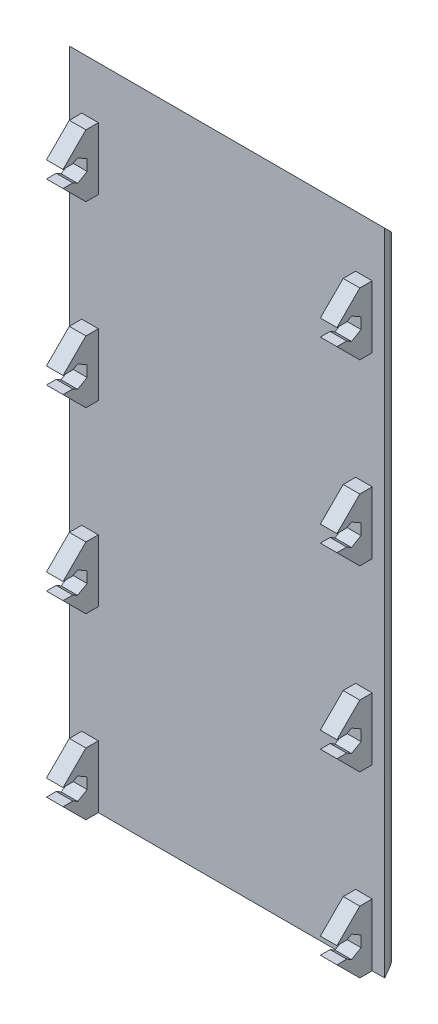
SolidWorks part; units mm, degrees
ref_plane "Front Plane" through (0, 0, 0) normal (0, 0, 1) x (1, 0, 0)
ref_plane "Top Plane" through (0, 0, 0) normal (0, 1, 0) x (1, 0, 0)
ref_plane "Right Plane" through (0, 0, 0) normal (1, 0, 0) x (0, 0, -1)
sketch "Sketch1" plane through (0, 0, 0) normal (0, 1, 0) x (1, 0, 0)
  line L0 (-9.2151, 0) -> (-9.2151, -10)
  line L1 (-9.2151, -10) -> (-5.2151, -10)
  line L2 (-5.2151, -10) -> (-5.2151, 0)
  line L3 (-5.2151, 0) -> (56.7849, 0)
  line L4 (56.7849, 0) -> (56.7849, -10)
  line L5 (56.7849, -10) -> (60.7849, -10)
  line L6 (60.7849, -10) -> (60.7849, 0)
  line L7 (60.7849, 0) -> (63.7849, 0)
  line L8 (-9.2151, 0) -> (-12.2151, 0)
  line L9 (-12.2151, 0) -> (-8.1737, 7)
  line L10 (-8.1737, 7) -> (59.7434, 7)
  line L11 (59.7434, 7) -> (63.7849, 0)
  line L12 (25.7849, 7) -> (25.7849, 0) construction
  dimension "D1" = 3
  dimension "D2" = 10
  dimension "D3" = 70
  dimension "D4" = 7
  dimension "D5" = 4
  dimension "D6" = 60
extrude "Boss-Extrude1" add sketch "Sketch1" along normal blind 156.5
sketch "Sketch4" plane through (60.7849, 0, 0) normal (1, 0, 0) x (0, 0, -1)
  line L0 (0, 156.5) -> (0, 0) construction
  line L1 (-37.5185, 156.5) -> (0, 156.5)
  line L2 (-37.5185, 156.5) -> (-37.5185, 144)
  line L3 (-37.5185, 144) -> (0, 144)
  line L4 (0, 156.5) -> (0, 144)
  line L5 (-37.5185, 156.5) -> (0, 144) construction
  line L6 (-37.5185, 144) -> (0, 156.5) construction
  line L7 (-10, 156.5) -> (0, 156.5) construction
  point P0 (-18.7592, 150.25)
  dimension "D1" = 12.5
extrude "Cut-Extrude1" cut sketch "Sketch4" against normal through all
sketch "Sketch5" plane through (60.7849, 0, 0) normal (1, 0, 0) x (0, 0, -1)
  line L0 (0, 156.5) -> (0, 0) construction
  line L1 (-33.3149, 129) -> (0, 129)
  line L2 (-33.3149, 129) -> (-33.3149, 101)
  line L3 (-33.3149, 101) -> (0, 101)
  line L4 (0, 129) -> (0, 101)
  line L5 (-33.3149, 129) -> (0, 101) construction
  line L6 (-33.3149, 101) -> (0, 129) construction
  line L7 (-10, 144) -> (0, 144) construction
  point P0 (-16.6574, 115)
  dimension "D1" = 28
  dimension "D2" = 15
extrude "Cut-Extrude2" cut sketch "Sketch5" against normal through all
sketch "Sketch6" plane through (0, 0, 0) normal (1, 0, 0) x (0, 0, -1)
  line L0 (-10, 144) -> (-10, 129) construction
  line L1 (-2.7, 137.8279) -> (-5, 139.1558)
  line L2 (-5, 139.1558) -> (-7.3, 137.8279)
  line L3 (-7.3, 137.8279) -> (-7.3, 135.1721)
  line L4 (-7.3, 135.1721) -> (-5, 133.8442)
  line L5 (-5, 133.8442) -> (-2.7, 135.1721)
  line L6 (-2.7, 135.1721) -> (-2.7, 137.8279)
  line L7 (-10, 144) -> (0, 144) construction
  line L8 (-6.15, 138.4919) -> (-10, 138.4919)
  line L9 (-6.15, 134.5081) -> (-10, 134.5081)
  line L10 (-10, 134.5081) -> (-10, 138.4919)
  circle A1 centre (-5, 136.5) radius 2.3 construction
  dimension "D1" = 4.6
  dimension "D2" = 7.5
  dimension "D3" = 5
extrude "Cut-Extrude3" cut sketch "Sketch6" against normal through all and the other way through all contours L10 L9 L4 L3 L2 L8 | L5 L6 L1 L2 L3 L4 region at (0, 136.5, 5) region at (0, 136.5, 8.5351)
pattern_linear "LPattern1" count 4 spacing 43 along (0, -1, 0) of "Cut-Extrude2", "Cut-Extrude3"
chamfer "Chamfer3" distance 7 angle 45 1 edges at (25.7849, 156.5, -7)
fillet "Fillet1" radius 8 2 edges at (-8.1737, 74.75, -7) (59.7434, 74.75, -7)
chamfer "Chamfer5" distance 7 angle 45 16 edges at (58.7849, 43, 10) (58.7849, 144, 10) (58.7849, 129, 10) (-7.2151, 144, 10) (-7.2151, 129, 10) (-7.2151, 101, 10) (-7.2151, 86, 10) (58.7849, 101, 10) (58.7849, 86, 10) (58.7849, 58, 10) (58.7849, 0, 10) (58.7849, 15, 10) (-7.2151, 0, 10) (-7.2151, 15, 10) (-7.2151, 58, 10) (-7.2151, 43, 10)
sketch "Sketch7" plane through (0, 0, -7) normal (0, 0, -1) x (-1, 0, 0)
  line L8 (3.5549, 82.737) -> (-11.316, 82.737) construction
  line L14 (-11.316, 128.6101) -> (-40.2538, 128.6101) construction
  line L20 (-11.316, 128.6101) -> (-11.316, 82.737) construction
  line L22 (-40.2538, 128.6101) -> (-40.2538, 82.737) construction
  line L23 (-11.316, 82.737) -> (-40.2538, 82.737) construction
  line L24 (3.5549, 0) -> (3.5549, 149.5) construction
  line L25 (-11.316, 127.6101) -> (-11.316, 116.1874)
  line L26 (-12.316, 128.6101) -> (-39.2538, 128.6101)
  line L27 (-11.316, 115.6101) -> (-40.2538, 115.6101) construction
  line L28 (-40.2538, 127.6101) -> (-40.2538, 115.6101)
  line L29 (-40.2538, 82.737) -> (-55.1246, 82.737) construction
  line L30 (-55.1246, 149.5) -> (-55.1246, 0) construction
  line L31 (-11.316, 149.5) -> (-11.316, 128.6101) construction
  line L32 (3.5549, 149.5) -> (-55.1246, 149.5) construction
  line L35 (-11.316, 107.5272) -> (-17.816, 103.7744)
  line L38 (-25.316, 99.4443) -> (-39.7538, 91.1086)
  line L39 (-11.316, 107.5272) -> (-11.316, 93.237)
  line L40 (-40.2538, 90.2426) -> (-40.2538, 82.737)
  line L41 (-40.2538, 82.737) -> (-32.316, 87.3199)
  line L42 (-32.316, 87.3199) -> (-32.316, 93.237) construction
  line L43 (-18.316, 102.9084) -> (-18.316, 93.237)
  line L44 (-11.316, 93.237) -> (-32.316, 93.237) construction
  line L45 (-25.316, 99.4443) -> (-25.316, 93.237)
  line L46 (-18.316, 93.237) -> (-25.316, 93.237) construction
  line L47 (-39.7538, 107.2744) -> (-18.566, 119.5072)
  line L48 (-40.2538, 115.6101) -> (-40.2538, 106.9857) construction
  line L49 (-11.316, 82.737) -> (-40.2538, 82.737) construction
  line L50 (-40.2538, 106.4084) -> (-40.2538, 100.5631)
  line L51 (-32.316, 87.3199) -> (-30.9714, 88.0962)
  line L52 (-11.816, 115.3214) -> (-31.566, 103.9187)
  line L53 (-33.2538, 121.1101) -> (-33.2538, 119.3988)
  line L54 (-31.566, 103.0527) -> (-25.316, 99.4443)
  line L55 (-32.316, 95.4028) -> (-39.7538, 99.6971)
  line L56 (-33.5038, 118.9657) -> (-40.2538, 115.0686)
  line L57 (-40.2538, 115.0686) -> (-40.2538, 115.6101)
  line L58 (-32.7538, 121.6101) -> (-18.816, 121.6101)
  line L59 (-18.316, 121.1101) -> (-18.316, 119.9402)
  line L60 (-11.316, 121.6101) -> (-18.316, 121.6101) construction
  line L61 (-33.2538, 121.6101) -> (-40.2538, 121.6101) construction
  line L62 (-40.2538, 128.6101) -> (-11.316, 128.6101) construction
  line L63 (-11.316, 128.6101) -> (-11.316, 82.737) construction
  arc A7 (-11.316, 93.237) -> (-32.316, 93.237) centre (-21.816, 93.237) cw
  arc A8 (-18.316, 93.237) -> (-25.316, 93.237) centre (-21.816, 93.237) cw
  arc A9 (-17.816, 103.7744) -> (-18.316, 102.9084) centre (-17.316, 102.9084) ccw
  arc A10 (-11.816, 115.3214) -> (-11.316, 116.1874) centre (-12.316, 116.1874) ccw
  arc A11 (-11.316, 127.6101) -> (-12.316, 128.6101) centre (-12.316, 127.6101) ccw
  arc A12 (-39.7538, 91.1086) -> (-40.2538, 90.2426) centre (-39.2538, 90.2426) ccw
  arc A13 (-39.2538, 128.6101) -> (-40.2538, 127.6101) centre (-39.2538, 127.6101) ccw
  arc A14 (-40.2538, 106.4084) -> (-39.7538, 107.2744) centre (-39.2538, 106.4084) cw
  arc A15 (-39.7538, 99.6971) -> (-40.2538, 100.5631) centre (-39.2538, 100.5631) cw
  arc A16 (-32.7538, 121.6101) -> (-33.2538, 121.1101) centre (-32.7538, 121.1101) ccw
  arc A17 (-33.5038, 118.9657) -> (-33.2538, 119.3988) centre (-33.7538, 119.3988) ccw
  arc A18 (-18.316, 121.1101) -> (-18.816, 121.6101) centre (-18.816, 121.1101) ccw
  arc A19 (-18.566, 119.5072) -> (-18.316, 119.9402) centre (-18.816, 119.9402) ccw
  arc A20 (-31.566, 103.0527) -> (-31.566, 103.9187) centre (-31.316, 103.4857) cw
  point P59 (-40.2538, 106.9857)
  point P63 (-40.2538, 99.9857)
  dimension "D11" = 7
  dimension "D12" = 30
  dimension "D10" = 7
  dimension "D14" = 0.5
  dimension "D16" = 7
  dimension "D6" = 7
  dimension "D13" = 1
  dimension "D2" = 1
  dimension "0.5" = 1
  dimension "D18" = 1
  dimension "D4" = 0.5
  dimension "D1" = 7
  dimension "D3" = 7
  dimension "D5" = 7
  dimension "D7" = 7
  dimension "D8" = 7
  dimension "D9" = 7
  dimension "D15" = 30
  dimension "D17" = 7
extrude "Cut-Extrude4" cut sketch "Sketch7" against normal blind 1 contours L54 A20 L52 A10 L25 A11 L26 A13 L28 L57 L56 L53 L58 L59 L47 A14 L50 A15 L55 L38 | L38 A12 L40 L41 L51 A7 L39 L35 A9 L43 A8 L45 region at (11.7564, 121.8988, -7) region at (25.697, 96.3406, -7)
sketch "Sketch8" plane through (0, 0, -7) normal (0, 0, -1) x (-1, 0, 0)
  line L0 (-40.2538, 128.6101) -> (-40.2538, 50.6101) construction
  line L1 (-55.1246, 149.5) -> (-55.1246, 0) construction
  line L2 (-25.7849, 128.6101) -> (-55.1246, 128.6101) construction
  line L3 (-12.316, 128.6101) -> (-39.2538, 128.6101) construction
  line L5 (-40.2538, 127.6101) -> (-40.2538, 115.0686) construction
  text T0 "DREam" font "VALORANT" height in points 14
  dimension "D1" = 78
extrude "Cut-Extrude5" cut sketch "Sketch8" against normal blind 1
fillet "Fillet2" radius 0.5 2 edges at (32.316, 95.4028, -6.5) (25.316, 99.4443, -6.5)
